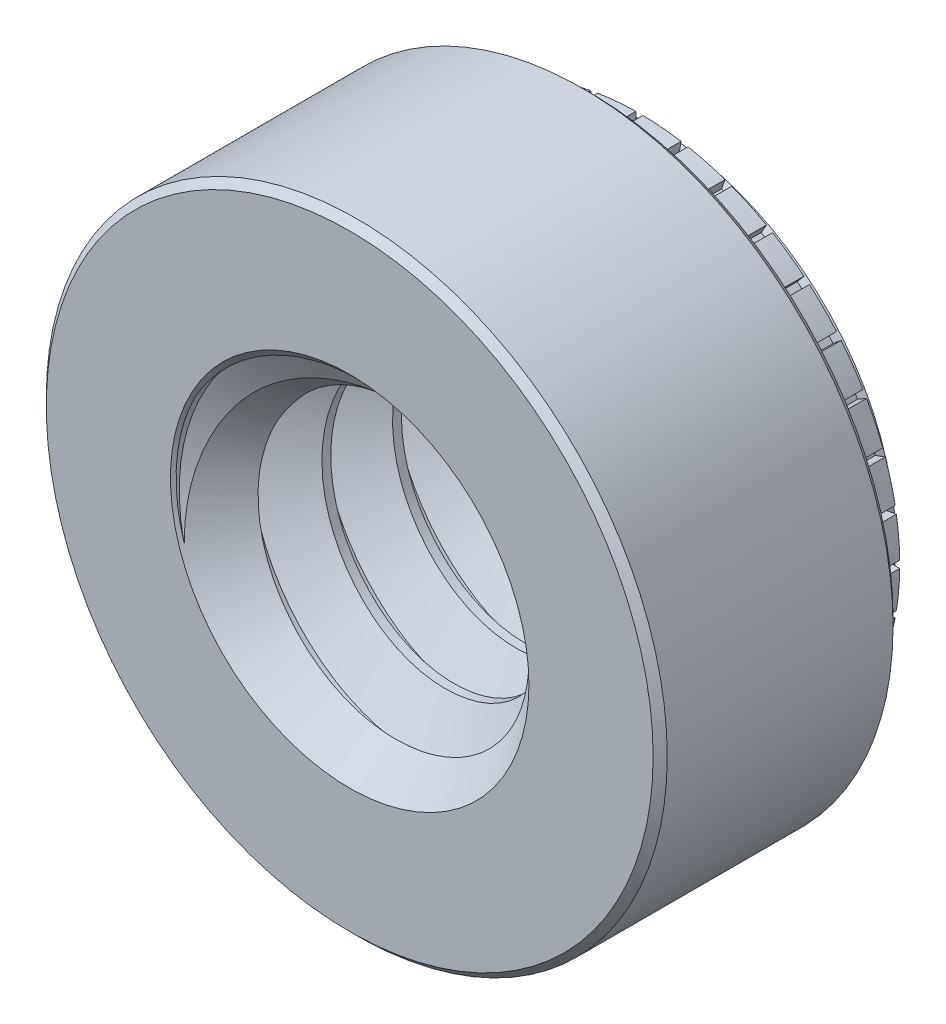
SolidWorks part; units mm, degrees
ref_plane "Front Plane" through (0, 0, 0) normal (0, 0, 1) x (1, 0, 0)
ref_plane "Top Plane" through (0, 0, 0) normal (0, 1, 0) x (1, 0, 0)
ref_plane "Right Plane" through (0, 0, 0) normal (1, 0, 0) x (0, 0, -1)
sketch "Sketch1" plane through (0, 0, 0) normal (0, 0, 1) x (1, 0, 0)
  circle A0 centre (0, 0) radius 5.588
  dimension "A" = 11.176
extrude "Extrude1" add sketch "Sketch1" against normal blind 4.318
sketch "Sketch15" plane through (0, 0, -4.318) normal (0, 0, -1) x (-1, 0, 0)
  circle A0 centre (0, 0) radius 4.3688
  dimension "hole dia" = 8.7376
sketch "Sketch2" plane through (0, 0, -4.318) normal (0, 0, -1) x (-1, 0, 0)
  circle A0 centre (0, 0) radius 4.6863
  dimension "D1" = 9.3726
extrude "Extrude2" add sketch "Sketch2" along normal blind 1.1938
sketch "Sketch3" plane through (0, 0, -5.5118) normal (0, 0, -1) x (-1, 0, 0)
  line L0 (0, 4.4958) -> (0, 5.588)
  circle A1 centre (0, 0) radius 5.588 construction
  circle A2 centre (0, 0) radius 4.4958
  circle A3 centre (0, 0) radius 4.4958 construction
  dimension "D1" = 0.1905
extrude "Cut-Extrude-Thin1" cut sketch "Sketch3" against normal up to surface (1.1938 mm away) thin up to face at (5.588, 0, -4.318) thin type mid plane wall 0.127
pattern_circular "CirPattern1" count 36 over 360 about axis through (0, 0, 0) along (0, 0, 1) of "Cut-Extrude-Thin1"
sketch "Sketch5" plane through (0, 0, -5.5118) normal (0, 0, -1) x (-1, 0, 0)
  circle A0 centre (0, 0) radius 5.588 construction
  circle A3 centre (0, 0) radius 4.318
  dimension "C" = 8.636
extrude "Cut-Extrude1" cut sketch "Sketch5" against normal blind 0.2984 draft 20 flip side to cut draft outward yes
chamfer "Chamfer2" distance 0.127 angle 45 2 edges at (5.588, 0, 0) (5.588, 0, -4.318)
sketch "Sketch7" plane through (0, 0, 0) normal (0, 0, 1) x (1, 0, 0)
  circle A0 centre (0, 0) radius 3.175
  dimension "Thread Od" = 6.35
extrude "Cut-Extrude3" cut sketch "Sketch7" against normal through all
sketch "Sketch8" plane through (0, 0, -5.5118) normal (0, 0, -1) x (-1, 0, 0)
  circle A0 centre (0, 0) radius 3.175 construction
  circle A1 centre (0, 0) radius 3.175
curve "Helix/Spiral1" pitch 1.27 height 8.6868 turns 6.84 parameters "pitch"=1.27
sketch "Sketch9" plane through (0, 0, 0) normal (1, 0, 0) x (0, 0, -1)
  line L0 (6.623, 3.175) -> (6.1468, 2.3501)
  line L1 (6.1468, 2.3501) -> (5.9881, 2.3501)
  line L2 (5.9881, 2.3501) -> (5.5118, 3.175)
  line L3 (6.623, 3.175) -> (5.5118, 3.175)
  line L4 (6.0674, 3.175) -> (6.0674, 2.3501) construction
  line L5 (6.3849, 2.7626) -> (5.7499, 2.7626) construction
  line L6 (5.5118, -3.175) -> (5.5118, 3.175) construction
  dimension "D1" = 60
  dimension "D2" = 0.1588
  dimension "D3" = 0.635
sweep "Sweep1" add profiles "Sketch9" path "Helix/Spiral1"
sketch "Sketch10" plane through (0, 0, 0) normal (0, 0, 1) x (1, 0, 0)
  circle A0 centre (0, 0) radius 5.588 construction
  circle A1 centre (0, 0) radius 5.588
extrude "Cut-Extrude4" cut sketch "Sketch10" along normal through all
sketch "Sketch11" plane through (0, 0, -5.5118) normal (0, 0, -1) x (-1, 0, 0)
  circle A1 centre (0, 0) radius 4.318 construction
  circle A2 centre (0, 0) radius 4.318
extrude "Cut-Extrude5" cut sketch "Sketch11" along normal through all
sketch "Sketch13" plane through (0, 0, 0) normal (0, 0, 1) x (1, 0, 0)
  circle A2 centre (0, 0) radius 3.2258
  circle A3 centre (0, 0) radius 3.2258
  dimension "D1" = 0.0508
extrude "Cut-Extrude6" cut sketch "Sketch13" against normal through all draft 45
sketch "Sketch14" plane through (0, 0, -5.5118) normal (0, 0, -1) x (-1, 0, 0)
  circle A2 centre (0, 0) radius 3.2258
  circle A3 centre (0, 0) radius 3.2258
  dimension "D1" = 0.0508
extrude "Cut-Extrude7" cut sketch "Sketch14" against normal through all draft 45
equation "\"D3@Helix/Spiral1\" = \"B@Extrude1\"+\"panel min.@Extrude2\"+.125"
equation "\"D2@Sketch9\" = \"pitch@Helix/Spiral1\"*.125"
equation "\"D3@Sketch9\" = \"pitch@Helix/Spiral1\"*.50"
equation "\"D1@Sketch2\" = \"hole dia@Sketch15\"+.025"
equation "\"D1@Cut-Extrude1\" = \"panel min.@Extrude2\"*.25"
